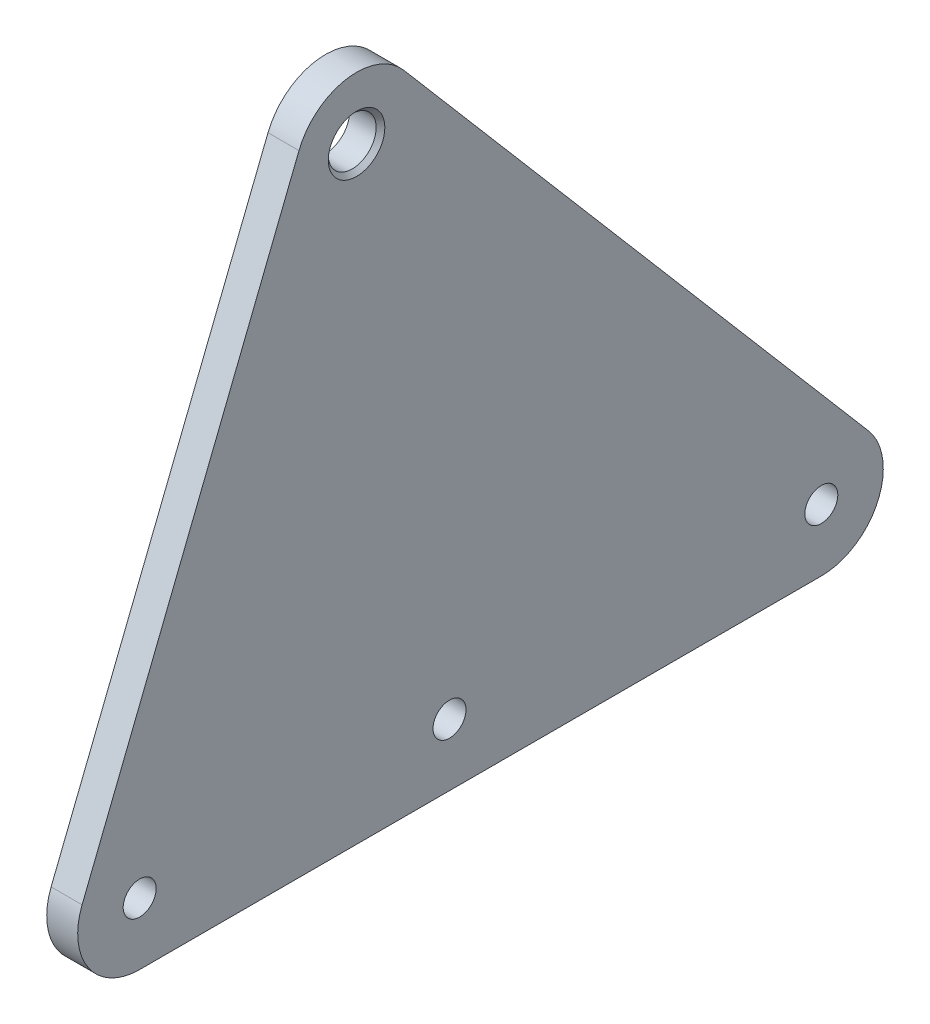
SolidWorks part; units mm, degrees
material "1060 Alloy"
ref_plane "Front Plane" through (0, 0, 0) normal (0, 0, 1) x (1, 0, 0)
ref_plane "Top Plane" through (0, 0, 0) normal (0, 1, 0) x (1, 0, 0)
ref_plane "Right Plane" through (0, 0, 0) normal (1, 0, 0) x (0, 0, -1)
sketch "Sketch1" plane through (0, 0, 0) normal (1, 0, 0) x (0, 0, -1)
  line L0 (-56.249, -106.9349) -> (-11.799, 4.6981)
  line L1 (9.6612, 8.2433) -> (104.9112, -103.3897)
  line L2 (-44.45, -124.333) -> (95.25, -124.333)
  arc A0 (9.6612, 8.2433) -> (-11.799, 4.6981) centre (0, 0) ccw
  arc A1 (95.25, -124.333) -> (104.9112, -103.3897) centre (95.25, -111.633) ccw
  arc A2 (-56.249, -106.9349) -> (-44.45, -124.333) centre (-44.45, -111.633) ccw
  dimension "D1" = 139.7
  dimension "D2" = 111.633
  dimension "D3" = 44.45
  dimension "D4" = 25.4
extrude "Boss-Extrude1" add sketch "Sketch1" along normal blind 6.35 contours L1 A1 L2 A2 L0 A0
sketch "Sketch2" plane through (6.35, 0, 0) normal (1, 0, 0) x (0, 0, -1)
  circle A0 centre (-44.45, -111.633) radius 3.3782
  circle A1 centre (19.05, -111.633) radius 3.3782
  circle A2 centre (95.25, -111.633) radius 3.3782
  arc A3 (-56.249, -106.9349) -> (-44.45, -124.333) centre (-44.45, -111.633) ccw construction
  arc A4 (95.25, -124.333) -> (104.9112, -103.3897) centre (95.25, -111.633) ccw construction
  dimension "D2" = 0
  dimension "D3" = 0
  dimension "D4" = 63.5
  dimension "D5" = 6.7564
extrude "Cut-Extrude1" cut sketch "Sketch2" against normal up to next
hole_wizard "3/8 Clearance Hole1" positions "Sketch3" profile "Sketch4" hole size "3/8" standard "ANSI Inch" end condition through all
sketch "Sketch3" plane through (6.35, 0, 0) normal (1, 0, 0) x (0, 0, -1)
  point P0 (0, 0)
sketch "Sketch4" plane through (6.35, 0, 0) normal (0, 1, 0) x (0, 0, -1)
  line L0 (0, 0) -> (0, 6.35)
  line L1 (0, 6.35) -> (4.9022, 6.35)
  line L2 (4.9022, 6.35) -> (4.9022, 0.8915)
  line L3 (4.9022, 0.8915) -> (5.7937, 0)
  line L5 (5.7937, 0) -> (0, 0)
  line L6 (-4.9022, 0.8915) -> (-5.7937, 0) construction
  line L11 (0, -6.35) -> (0, 107.95) construction
  dimension "Thru Hole Dia." = 9.8044
  dimension "Thru Hole Depth" = 6.35
  dimension "Near C'Sink Dia." = 11.5875
  dimension "Near C'Sink Angle" = 90
